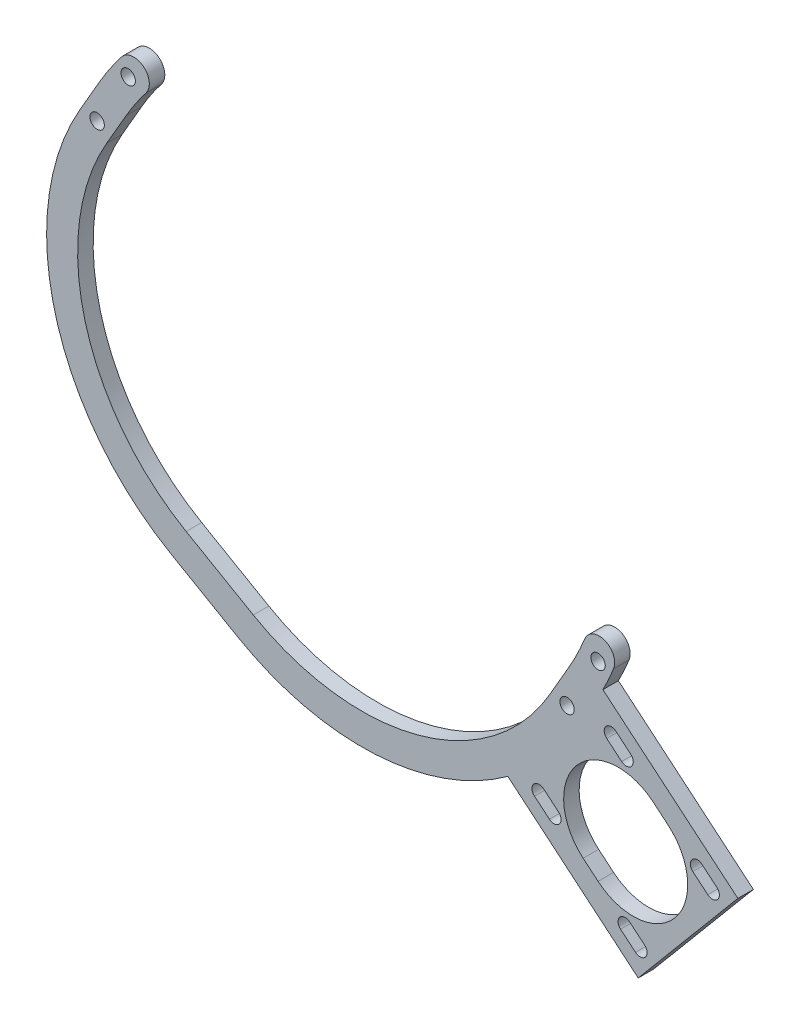
SolidWorks part; units mm, degrees
ref_plane "Front Plane" through (0, 0, 0) normal (0, 0, 1) x (1, 0, 0)
ref_plane "Top Plane" through (0, 0, 0) normal (0, 1, 0) x (1, 0, 0)
ref_plane "Right Plane" through (0, 0, 0) normal (1, 0, 0) x (0, 0, -1)
sketch "Sketch1" plane through (0, 0, -14.157) normal (0, 0, -1) x (-1, 0, 0)
  line L0 (-49.1723, -34.5021) -> (-53.1411, -27.628)
  line L1 (-2.2729, 1.7407) -> (29.3872, -53.0962) construction
  line L2 (20.2218, -53.0962) -> (27.0959, -49.1274)
  line L3 (33.9699, -45.1587) -> (20.2218, -53.0962) construction
  line L4 (17.0468, -47.5969) -> (23.9209, -43.6282)
  line L5 (-43.6731, -31.3271) -> (-47.6418, -24.453)
  line L6 (47.0648, 21.0604) -> (43.096, 27.9345)
  line L7 (30.7949, -39.6594) -> (23.9209, -43.6282)
  line L8 (33.9699, -45.1587) -> (27.0959, -49.1274)
  line L9 (52.564, 24.2354) -> (48.5953, 31.1095)
  arc A0 (-53.1411, -27.628) -> (-56.7299, -20.2712) centre (-2.2729, 1.7407) cw
  arc A3 (-61.0104, 1.7407) -> (-53.1411, -27.628) centre (-2.2729, 1.7407) ccw construction
  circle A4 centre (-53.5664, -20.5413) radius 1.1303 construction
  arc A5 (-49.1723, -34.5021) -> (20.2218, -53.0962) centre (-5.1782, -9.1021) ccw
  arc A6 (-43.6731, -31.3271) -> (17.0468, -47.5969) centre (-5.1782, -9.1021) ccw
  arc A7 (-47.6418, -24.453) -> (-50.8427, -17.8916) centre (-2.2729, 1.7407) cw
  arc A8 (-56.7299, -20.2712) -> (-50.8427, -17.8916) centre (-53.7863, -19.0814) cw
  arc A9 (44.0185, 37.8959) -> (39.014, 33.9872) centre (41.5163, 35.9416) ccw
  arc A10 (43.096, 27.9345) -> (39.014, 33.9872) centre (-2.2729, 1.7407) ccw
  arc A11 (47.0648, 21.0604) -> (30.7949, -39.6594) centre (8.5699, -1.1646) cw
  arc A12 (52.564, 24.2354) -> (33.9699, -45.1587) centre (8.5699, -1.1646) cw
  arc A13 (48.5953, 31.1095) -> (44.0185, 37.8959) centre (-2.2729, 1.7407) ccw
  dimension "D1" = 3.175
  dimension "D2" = 6.35
extrude "Boss-Extrude1" add sketch "Sketch1" along normal blind 3.175
ref_plane "Plane1" through (0, -58.42, 0) normal (0, 1, 0) x (-1, 0, 0)
ref_plane "Plane2" through (0, 0, -14.157) normal (0, 0, 1) x (1, 0, 0)
ref_axis "Axis2" through (-66.4483, 0, -14.157) along (1, 0, 0)
ref_axis "Axis3" through (0, 0, -25.4783) along (0, 0, 1)
ref_point "Point1"
ref_axis "Axis4" through (0, -70.9509, -14.157) along (0, 1, 0)
sketch "Sketch6" plane through (0, 0, -14.157) normal (0, 0, 1) x (1, 0, 0)
  line L0 (0, 0) -> (56.7821, -47.6458) construction
  line L1 (0, -70.9509) -> (0, 0.8498) construction
  line L10 (82.1971, -48.2482) -> (61.7886, -72.5701)
  line L15 (82.1971, -48.2482) -> (51.7755, -22.7215)
  line L16 (61.7886, -72.5701) -> (31.367, -47.0434)
  line L17 (51.7755, -22.7215) -> (31.367, -47.0434)
  line L18 (82.1971, -48.2482) -> (31.367, -47.0434) construction
  line L19 (61.7886, -72.5701) -> (51.7755, -22.7215) construction
  line L20 (57.6916, -48.409) -> (60.7464, -50.9723) construction
  line L21 (64.8754, -39.8477) -> (67.9302, -42.411)
  line L22 (50.5078, -56.9703) -> (53.5626, -59.5336)
  line L23 (40.152, -48.7118) -> (66.3946, -70.732) construction
  line L24 (62.1646, -67.1826) -> (59.1098, -64.6193) construction
  line L25 (80.7131, -52.7061) -> (54.0574, -30.3393) construction
  line L26 (61.234, -68.2917) -> (58.1792, -65.7284)
  line L27 (63.0953, -66.0735) -> (60.0404, -63.5102)
  line L28 (41.4813, -49.8272) -> (44.5361, -52.3905) construction
  line L29 (42.4119, -48.7181) -> (45.4667, -51.2814)
  line L30 (40.5506, -50.9363) -> (43.6055, -53.4996)
  line L31 (56.2734, -32.1987) -> (59.3282, -34.762) construction
  line L32 (57.204, -31.0896) -> (60.2588, -33.6529)
  line L33 (55.3427, -33.3078) -> (58.3976, -35.8711)
  line L34 (73.9019, -46.9908) -> (76.9567, -49.5541) construction
  line L35 (74.8325, -45.8817) -> (77.8873, -48.445)
  line L36 (72.9712, -48.0998) -> (76.0261, -50.6631)
  line L37 (44.5361, -52.3905) -> (59.3282, -34.762) construction
  arc A0 (61.234, -68.2917) -> (63.0953, -66.0735) centre (62.1646, -67.1826) ccw
  arc A1 (60.0404, -63.5102) -> (58.1792, -65.7284) centre (59.1098, -64.6193) ccw
  arc A2 (-17.0468, -47.5969) -> (43.6731, -31.3271) centre (5.1782, -9.1021) ccw construction
  arc A3 (64.8754, -39.8477) -> (50.5078, -56.9703) centre (57.6916, -48.409) ccw
  arc A4 (53.5626, -59.5336) -> (67.9302, -42.411) centre (60.7464, -50.9723) ccw
  arc A5 (42.4119, -48.7181) -> (40.5506, -50.9363) centre (41.4813, -49.8272) ccw
  arc A6 (43.6055, -53.4996) -> (45.4667, -51.2814) centre (44.5361, -52.3905) ccw
  arc A7 (57.204, -31.0896) -> (55.3427, -33.3078) centre (56.2734, -32.1987) ccw
  arc A8 (58.3976, -35.8711) -> (60.2588, -33.6529) centre (59.3282, -34.762) ccw
  arc A9 (74.8325, -45.8817) -> (72.9712, -48.0998) centre (73.9019, -46.9908) ccw
  arc A10 (76.0261, -50.6631) -> (77.8873, -48.445) centre (76.9567, -49.5541) ccw
  point P3 (59.219, -49.6906)
  point P25 (60.6372, -65.9009)
  point P30 (43.0087, -51.1088)
  point P37 (57.8008, -33.4803)
  point P44 (75.4293, -48.2724)
  dimension "D4" = 11.176
  dimension "D5" = 11.5062
  dimension "D8" = 1.4478
  dimension "D9" = 23.0124
  dimension "D14" = 1.4478
  dimension "D15" = 1.4478
  dimension "D16" = 1.4478
  dimension "D19" = 3.9878
  dimension "D1" = 50
  dimension "D2" = 93.98
  dimension "D3" = 31.75
  dimension "D6" = 11.5062
  dimension "D7" = 3.9878
  dimension "D10" = 23.0124
  dimension "D11" = 3.9878
  dimension "D12" = 3.9878
  dimension "D13" = 3.9878
  dimension "D17" = 3.175
  dimension "D18" = 3.175
  dimension "D20" = 11.5062
extrude "Boss-Extrude2" add sketch "Sketch6" against normal up to surface (3.175 mm away) up to face at (-5.7343, -12.1282, -17.332)
hole_wizard "#4 Clearance Hole1" positions "Sketch5" profile "Sketch4" hole size "#4" standard "Ansi Inch" end condition through all
sketch "Sketch5" plane through (0, 0, -17.332) normal (0, 0, -1) x (-1, 0, 0)
  circle A1 centre (-53.5664, -20.5413) radius 1.1303 construction
  circle A2 centre (49.0206, 24.0227) radius 1.1303 construction
  point P0 (-53.5664, -20.5413)
  point P5 (-47.2164, -31.5398)
  point P8 (42.6706, 35.0212)
  point P11 (49.0206, 24.0227)
sketch "Sketch4" plane through (53.5664, -20.5413, -17.332) normal (1, 0, 0) x (0, 1, 0)
  line L0 (0, 0) -> (0, 3.175)
  line L1 (0, 3.175) -> (1.4732, 3.175)
  line L2 (1.4732, 3.175) -> (1.4732, 0)
  line L5 (1.4732, 0) -> (0, 0)
  line L11 (0, -6.35) -> (0, 107.95) construction
  dimension "Thru Hole Dia." = 2.9464
  dimension "Thru Hole Depth" = 3.175
